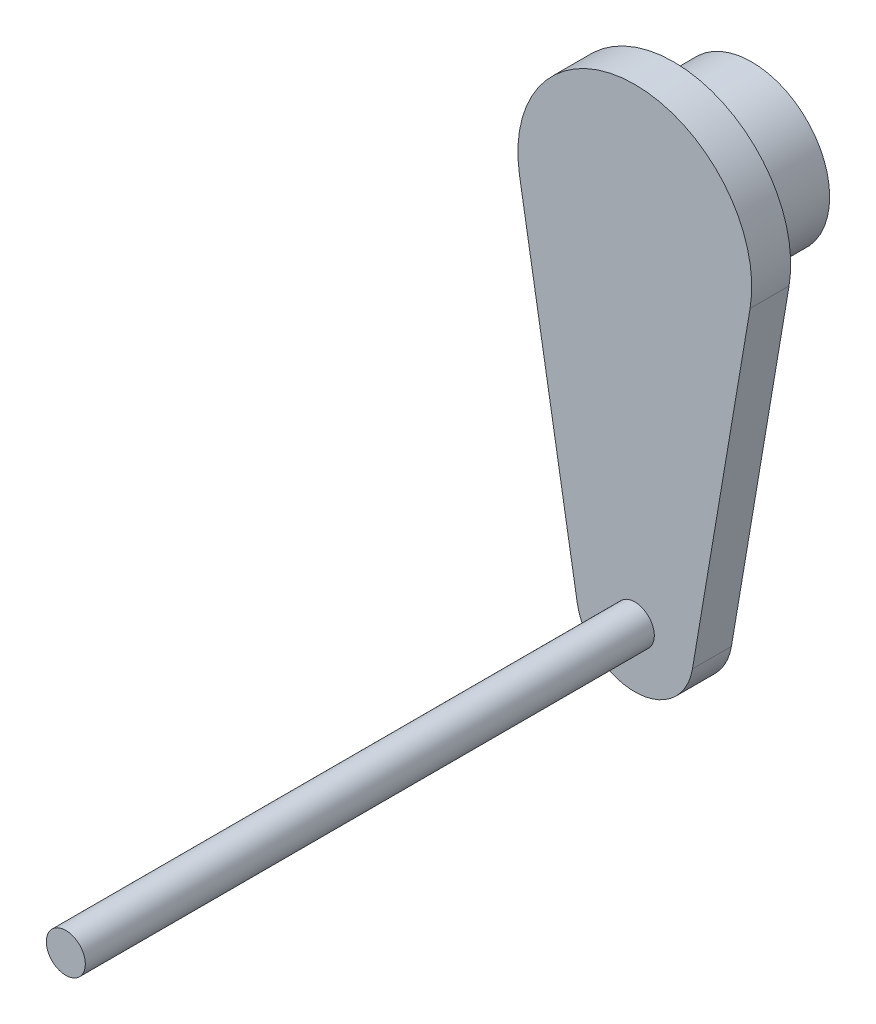
SolidWorks part; units mm, degrees
ref_plane "Front Plane" through (0, 0, 0) normal (0, 0, 1) x (1, 0, 0)
ref_plane "Top Plane" through (0, 0, 0) normal (0, 1, 0) x (1, 0, 0)
ref_plane "Right Plane" through (0, 0, 0) normal (1, 0, 0) x (0, 0, -1)
sketch "Sketch1" plane through (0, 0, 0) normal (0, 0, 1) x (1, 0, 0)
  line L0 (0, 0) -> (0, -57.15) construction
  line L1 (18.7836, -3.175) -> (9.3918, -58.7375)
  line L2 (-18.7836, -3.175) -> (-9.3918, -58.7375)
  circle A0 centre (0, 0) radius 12.7 construction
  circle A1 centre (0, 0) radius 12.7
  circle A2 centre (0, 0) radius 57.15 construction
  circle A3 centre (0, -57.15) radius 3.175
  arc A4 (18.7836, -3.175) -> (-18.7836, -3.175) centre (0, 0) ccw
  arc A5 (-9.4919, -56.3563) -> (9.4919, -56.3563) centre (0, -57.15) ccw
  arc A6 (0, -19.05) -> (18.7836, -3.175) centre (0, 0) ccw construction
  circle A7 centre (0, 0) radius 19.05 construction
  arc A8 (-18.7836, -3.175) -> (0, -19.05) centre (0, 0) ccw construction
  arc A9 (9.4919, -56.3563) -> (0, -47.625) centre (0, -57.15) ccw construction
  circle A10 centre (0, -57.15) radius 9.525 construction
  arc A11 (0, -47.625) -> (-9.4919, -56.3563) centre (0, -57.15) ccw construction
  dimension "D1" = 114.3
  dimension "D2" = 6.35
  dimension "D3" = 6.35
extrude "Boss-Extrude1" add sketch "Sketch1" against normal up to surface (12.7 mm away) contours A1
extrude "Boss-Extrude2" add sketch "Sketch1<3>" along normal blind 6.35 contours A1 | L2 A5 L1 A4 A1 A3 region at (0, -24.2505, 0) region at (0, 0, 0)
sketch "Sketch1<3>" plane through (0, 0, 0) normal (0, 0, 1) x (1, 0, 0) same geometry as "Sketch1"
extrude "Boss-Extrude3" add sketch "Sketch1<4>" along normal offset from surface (99.06 mm away) 2.54 contours A3
sketch "Sketch1<4>" plane through (0, 0, 0) normal (0, 0, 1) x (1, 0, 0) same geometry as "Sketch1"
ref_axis "Axis1" through (0, -57.15, 99.06) along (0, 0, -1)
ref_point "Point2"
equation "\"D1@Sketch1\"=\"MaxSpinnerDiameter@ConceptAssem_2.Assembly\""
equation "\"RodDiameter\"= \"D2@Sketch1\""
